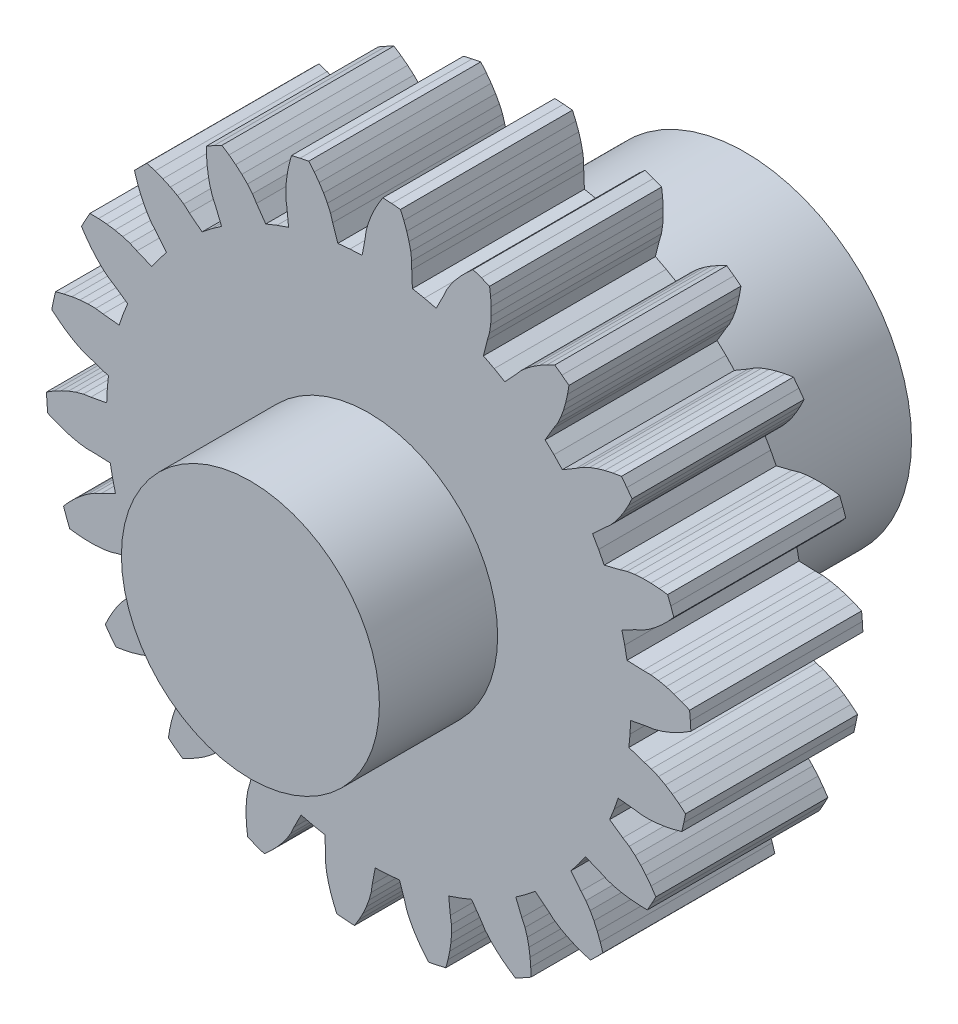
SolidWorks part; units mm, degrees
ref_plane "Front Plane" through (0, 0, 0) normal (0, 0, 1) x (1, 0, 0)
ref_plane "Top Plane" through (0, 0, 0) normal (0, 1, 0) x (1, 0, 0)
ref_plane "Right Plane" through (0, 0, 0) normal (1, 0, 0) x (0, 0, -1)
sketch "Sketch1" plane through (0, 0, 0) normal (0, 0, 1) x (1, 0, 0)
  line L0 (24.3674, -0.607) -> (25.8394, -0.3335)
  line L1 (25.8394, -0.3335) -> (26.5336, -0.2338)
  line L2 (26.5336, -0.2338) -> (27.2277, -0.0399)
  line L3 (27.2277, -0.0399) -> (27.9199, 0.2199)
  line L4 (27.9199, 0.2199) -> (28.6088, 0.536)
  line L5 (28.6088, 0.536) -> (29.293, 0.9035)
  line L6 (29.293, 0.9035) -> (29.971, 1.319)
  line L7 (29.971, 1.319) -> (29.9236, 2.1402)
  line L8 (29.9236, 2.1402) -> (29.8536, 2.9597)
  line L9 (29.8536, 2.9597) -> (29.1234, 3.2745)
  line L10 (29.1234, 3.2745) -> (28.3939, 3.5409)
  line L11 (28.3939, 3.5409) -> (27.667, 3.7558)
  line L12 (27.667, 3.7558) -> (26.9449, 3.9144)
  line L13 (26.9449, 3.9144) -> (26.2302, 4.0076)
  line L14 (26.2302, 4.0076) -> (25.5289, 4.0074)
  line L15 (25.5289, 4.0074) -> (24.033, 4.0687)
  line L16 (24.033, 4.0687) -> (23.818, 5.1813)
  line L17 (23.818, 5.1813) -> (23.5514, 6.2827)
  line L18 (23.5514, 6.2827) -> (24.8867, 6.9598)
  line L19 (24.8867, 6.9598) -> (25.5247, 7.251)
  line L20 (25.5247, 7.251) -> (26.136, 7.6327)
  line L21 (26.136, 7.6327) -> (26.727, 8.0769)
  line L22 (26.727, 8.0769) -> (27.299, 8.5743)
  line L23 (27.299, 8.5743) -> (27.8519, 9.1197)
  line L24 (27.8519, 9.1197) -> (28.3853, 9.7094)
  line L25 (28.3853, 9.7094) -> (28.1085, 10.4839)
  line L26 (28.1085, 10.4839) -> (27.8105, 11.2506)
  line L27 (27.8105, 11.2506) -> (27.0212, 11.3469)
  line L28 (27.0212, 11.3469) -> (26.2462, 11.397)
  line L29 (26.2462, 11.397) -> (25.4882, 11.3984)
  line L30 (25.4882, 11.3984) -> (24.7506, 11.347)
  line L31 (24.7506, 11.347) -> (24.0387, 11.2352)
  line L32 (24.0387, 11.2352) -> (23.3658, 11.0374)
  line L33 (23.3658, 11.0374) -> (21.9133, 10.6747)
  line L34 (21.9133, 10.6747) -> (21.3934, 11.6817)
  line L35 (21.3934, 11.6817) -> (20.8274, 12.6634)
  line L36 (20.8274, 12.6634) -> (21.9178, 13.6893)
  line L37 (21.9178, 13.6893) -> (22.4479, 14.1484)
  line L38 (22.4479, 14.1484) -> (22.9269, 14.6868)
  line L39 (22.9269, 14.6868) -> (23.3689, 15.2796)
  line L40 (23.3689, 15.2796) -> (23.7775, 15.918)
  line L41 (23.7775, 15.918) -> (24.1544, 16.597)
  line L42 (24.1544, 16.597) -> (24.5001, 17.3132)
  line L43 (24.5001, 17.3132) -> (24.0162, 17.9783)
  line L44 (24.0162, 17.9783) -> (23.5144, 18.63)
  line L45 (23.5144, 18.63) -> (22.7298, 18.5)
  line L46 (22.7298, 18.5) -> (21.9721, 18.3297)
  line L47 (21.9721, 18.3297) -> (21.2444, 18.1175)
  line L48 (21.2444, 18.1175) -> (20.5512, 17.8605)
  line L49 (20.5512, 17.8605) -> (19.8996, 17.5525)
  line L50 (19.8996, 17.5525) -> (19.3097, 17.1732)
  line L51 (19.3097, 17.1732) -> (18.0182, 16.416)
  line L52 (18.0182, 16.416) -> (17.2357, 17.2357)
  line L53 (17.2357, 17.2357) -> (16.416, 18.0182)
  line L54 (16.416, 18.0182) -> (17.1732, 19.3097)
  line L55 (17.1732, 19.3097) -> (17.5525, 19.8996)
  line L56 (17.5525, 19.8996) -> (17.8605, 20.5512)
  line L57 (17.8605, 20.5512) -> (18.1175, 21.2444)
  line L58 (18.1175, 21.2444) -> (18.3297, 21.9721)
  line L59 (18.3297, 21.9721) -> (18.5, 22.7298)
  line L60 (18.5, 22.7298) -> (18.63, 23.5144)
  line L61 (18.63, 23.5144) -> (17.9783, 24.0162)
  line L62 (17.9783, 24.0162) -> (17.3132, 24.5001)
  line L63 (17.3132, 24.5001) -> (16.597, 24.1544)
  line L64 (16.597, 24.1544) -> (15.918, 23.7775)
  line L65 (15.918, 23.7775) -> (15.2796, 23.3689)
  line L66 (15.2796, 23.3689) -> (14.6868, 22.9269)
  line L67 (14.6868, 22.9269) -> (14.1484, 22.4479)
  line L68 (14.1484, 22.4479) -> (13.6893, 21.9178)
  line L69 (13.6893, 21.9178) -> (12.6634, 20.8274)
  line L70 (12.6634, 20.8274) -> (11.6817, 21.3934)
  line L71 (11.6817, 21.3934) -> (10.6747, 21.9133)
  line L72 (10.6747, 21.9133) -> (11.0374, 23.3658)
  line L73 (11.0374, 23.3658) -> (11.2352, 24.0387)
  line L74 (11.2352, 24.0387) -> (11.347, 24.7506)
  line L75 (11.347, 24.7506) -> (11.3984, 25.4882)
  line L76 (11.3984, 25.4882) -> (11.397, 26.2462)
  line L77 (11.397, 26.2462) -> (11.3469, 27.0212)
  line L78 (11.3469, 27.0212) -> (11.2506, 27.8105)
  line L79 (11.2506, 27.8105) -> (10.4839, 28.1085)
  line L80 (10.4839, 28.1085) -> (9.7094, 28.3853)
  line L81 (9.7094, 28.3853) -> (9.1197, 27.8519)
  line L82 (9.1197, 27.8519) -> (8.5743, 27.299)
  line L83 (8.5743, 27.299) -> (8.0769, 26.727)
  line L84 (8.0769, 26.727) -> (7.6327, 26.136)
  line L85 (7.6327, 26.136) -> (7.251, 25.5247)
  line L86 (7.251, 25.5247) -> (6.9598, 24.8867)
  line L87 (6.9598, 24.8867) -> (6.2827, 23.5514)
  line L88 (6.2827, 23.5514) -> (5.1813, 23.818)
  line L89 (5.1813, 23.818) -> (4.0687, 24.033)
  line L90 (4.0687, 24.033) -> (4.0074, 25.5289)
  line L91 (4.0074, 25.5289) -> (4.0076, 26.2302)
  line L92 (4.0076, 26.2302) -> (3.9144, 26.9449)
  line L93 (3.9144, 26.9449) -> (3.7558, 27.667)
  line L94 (3.7558, 27.667) -> (3.5409, 28.3939)
  line L95 (3.5409, 28.3939) -> (3.2745, 29.1234)
  line L96 (3.2745, 29.1234) -> (2.9597, 29.8536)
  line L97 (2.9597, 29.8536) -> (2.1402, 29.9236)
  line L98 (2.1402, 29.9236) -> (1.319, 29.971)
  line L99 (1.319, 29.971) -> (0.9035, 29.293)
  line L100 (0.9035, 29.293) -> (0.536, 28.6088)
  line L101 (0.536, 28.6088) -> (0.2199, 27.9199)
  line L102 (0.2199, 27.9199) -> (-0.0399, 27.2277)
  line L103 (-0.0399, 27.2277) -> (-0.2338, 26.5336)
  line L104 (-0.2338, 26.5336) -> (-0.3335, 25.8394)
  line L105 (-0.3335, 25.8394) -> (-0.607, 24.3674)
  line L106 (-0.607, 24.3674) -> (-1.7389, 24.3129)
  line L107 (-1.7389, 24.3129) -> (-2.867, 24.2058)
  line L108 (-2.867, 24.2058) -> (-3.3473, 25.6238)
  line L109 (-3.3473, 25.6238) -> (-3.5447, 26.2968)
  line L110 (-3.5447, 26.2968) -> (-3.8354, 26.9562)
  line L111 (-3.8354, 26.9562) -> (-4.191, 27.6044)
  line L112 (-4.191, 27.6044) -> (-4.602, 28.2413)
  line L113 (-4.602, 28.2413) -> (-5.0631, 28.8663)
  line L114 (-5.0631, 28.8663) -> (-5.5709, 29.4782)
  line L115 (-5.5709, 29.4782) -> (-6.377, 29.3144)
  line L116 (-6.377, 29.3144) -> (-7.1782, 29.1286)
  line L117 (-7.1782, 29.1286) -> (-7.3859, 28.361)
  line L118 (-7.3859, 28.361) -> (-7.5457, 27.601)
  line L119 (-7.5457, 27.601) -> (-7.655, 26.8509)
  line L120 (-7.655, 26.8509) -> (-7.7092, 26.1135)
  line L121 (-7.7092, 26.1135) -> (-7.6997, 25.3929)
  line L122 (-7.6997, 25.3929) -> (-7.5998, 24.6988)
  line L123 (-7.5998, 24.6988) -> (-7.4475, 23.2094)
  line L124 (-7.4475, 23.2094) -> (-8.5182, 22.8381)
  line L125 (-8.5182, 22.8381) -> (-9.5705, 22.4176)
  line L126 (-9.5705, 22.4176) -> (-10.4307, 23.6429)
  line L127 (-10.4307, 23.6429) -> (-10.8098, 24.2329)
  line L128 (-10.8098, 24.2329) -> (-11.2745, 24.7837)
  line L129 (-11.2745, 24.7837) -> (-11.7983, 25.3055)
  line L130 (-11.7983, 25.3055) -> (-12.3721, 25.8008)
  line L131 (-12.3721, 25.8008) -> (-12.9906, 26.2705)
  line L132 (-12.9906, 26.2705) -> (-13.6502, 26.7146)
  line L133 (-13.6502, 26.7146) -> (-14.3775, 26.3304)
  line L134 (-14.3775, 26.3304) -> (-15.0939, 25.9263)
  line L135 (-15.0939, 25.9263) -> (-15.0769, 25.1313)
  line L136 (-15.0769, 25.1313) -> (-15.0162, 24.3571)
  line L137 (-15.0162, 24.3571) -> (-14.9097, 23.6066)
  line L138 (-14.9097, 23.6066) -> (-14.7539, 22.8838)
  line L139 (-14.7539, 22.8838) -> (-14.5419, 22.1951)
  line L140 (-14.5419, 22.1951) -> (-14.2504, 21.5572)
  line L141 (-14.2504, 21.5572) -> (-13.6847, 20.171)
  line L142 (-13.6847, 20.171) -> (-14.6074, 19.5132)
  line L143 (-14.6074, 19.5132) -> (-15.4986, 18.8132)
  line L144 (-15.4986, 18.8132) -> (-16.6692, 19.7465)
  line L145 (-16.6692, 19.7465) -> (-17.1991, 20.2059)
  line L146 (-17.1991, 20.2059) -> (-17.8002, 20.6034)
  line L147 (-17.8002, 20.6034) -> (-18.4498, 20.9565)
  line L148 (-18.4498, 20.9565) -> (-19.1399, 21.2701)
  line L149 (-19.1399, 21.2701) -> (-19.8656, 21.5465)
  line L150 (-19.8656, 21.5465) -> (-20.6237, 21.7868)
  line L151 (-20.6237, 21.7868) -> (-21.2132, 21.2132)
  line L152 (-21.2132, 21.2132) -> (-21.7868, 20.6237)
  line L153 (-21.7868, 20.6237) -> (-21.5465, 19.8656)
  line L154 (-21.5465, 19.8656) -> (-21.2701, 19.1399)
  line L155 (-21.2701, 19.1399) -> (-20.9565, 18.4498)
  line L156 (-20.9565, 18.4498) -> (-20.6034, 17.8002)
  line L157 (-20.6034, 17.8002) -> (-20.2059, 17.1991)
  line L158 (-20.2059, 17.1991) -> (-19.7465, 16.6692)
  line L159 (-19.7465, 16.6692) -> (-18.8132, 15.4986)
  line L160 (-18.8132, 15.4986) -> (-19.5132, 14.6074)
  line L161 (-19.5132, 14.6074) -> (-20.171, 13.6847)
  line L162 (-20.171, 13.6847) -> (-21.5572, 14.2504)
  line L163 (-21.5572, 14.2504) -> (-22.1951, 14.5419)
  line L164 (-22.1951, 14.5419) -> (-22.8838, 14.7539)
  line L165 (-22.8838, 14.7539) -> (-23.6066, 14.9097)
  line L166 (-23.6066, 14.9097) -> (-24.3571, 15.0162)
  line L167 (-24.3571, 15.0162) -> (-25.1313, 15.0769)
  line L168 (-25.1313, 15.0769) -> (-25.9263, 15.0939)
  line L169 (-25.9263, 15.0939) -> (-26.3304, 14.3775)
  line L170 (-26.3304, 14.3775) -> (-26.7146, 13.6502)
  line L171 (-26.7146, 13.6502) -> (-26.2705, 12.9906)
  line L172 (-26.2705, 12.9906) -> (-25.8008, 12.3721)
  line L173 (-25.8008, 12.3721) -> (-25.3055, 11.7983)
  line L174 (-25.3055, 11.7983) -> (-24.7837, 11.2745)
  line L175 (-24.7837, 11.2745) -> (-24.2329, 10.8098)
  line L176 (-24.2329, 10.8098) -> (-23.6429, 10.4307)
  line L177 (-23.6429, 10.4307) -> (-22.4176, 9.5705)
  line L178 (-22.4176, 9.5705) -> (-22.8381, 8.5182)
  line L179 (-22.8381, 8.5182) -> (-23.2094, 7.4475)
  line L180 (-23.2094, 7.4475) -> (-24.6988, 7.5998)
  line L181 (-24.6988, 7.5998) -> (-25.3929, 7.6997)
  line L182 (-25.3929, 7.6997) -> (-26.1135, 7.7092)
  line L183 (-26.1135, 7.7092) -> (-26.8509, 7.655)
  line L184 (-26.8509, 7.655) -> (-27.601, 7.5457)
  line L185 (-27.601, 7.5457) -> (-28.361, 7.3859)
  line L186 (-28.361, 7.3859) -> (-29.1286, 7.1782)
  line L187 (-29.1286, 7.1782) -> (-29.3144, 6.377)
  line L188 (-29.3144, 6.377) -> (-29.4782, 5.5709)
  line L189 (-29.4782, 5.5709) -> (-28.8663, 5.0631)
  line L190 (-28.8663, 5.0631) -> (-28.2413, 4.602)
  line L191 (-28.2413, 4.602) -> (-27.6044, 4.191)
  line L192 (-27.6044, 4.191) -> (-26.9562, 3.8354)
  line L193 (-26.9562, 3.8354) -> (-26.2968, 3.5447)
  line L194 (-26.2968, 3.5447) -> (-25.6238, 3.3473)
  line L195 (-25.6238, 3.3473) -> (-24.2058, 2.867)
  line L196 (-24.2058, 2.867) -> (-24.3129, 1.7389)
  line L197 (-24.3129, 1.7389) -> (-24.3674, 0.607)
  line L198 (-24.3674, 0.607) -> (-25.8394, 0.3335)
  line L199 (-25.8394, 0.3335) -> (-26.5336, 0.2338)
  line L200 (-26.5336, 0.2338) -> (-27.2277, 0.0399)
  line L201 (-27.2277, 0.0399) -> (-27.9199, -0.2199)
  line L202 (-27.9199, -0.2199) -> (-28.6088, -0.536)
  line L203 (-28.6088, -0.536) -> (-29.293, -0.9035)
  line L204 (-29.293, -0.9035) -> (-29.971, -1.319)
  line L205 (-29.971, -1.319) -> (-29.9236, -2.1402)
  line L206 (-29.9236, -2.1402) -> (-29.8536, -2.9597)
  line L207 (-29.8536, -2.9597) -> (-29.1234, -3.2745)
  line L208 (-29.1234, -3.2745) -> (-28.3939, -3.5409)
  line L209 (-28.3939, -3.5409) -> (-27.667, -3.7558)
  line L210 (-27.667, -3.7558) -> (-26.9449, -3.9144)
  line L211 (-26.9449, -3.9144) -> (-26.2302, -4.0076)
  line L212 (-26.2302, -4.0076) -> (-25.5289, -4.0074)
  line L213 (-25.5289, -4.0074) -> (-24.033, -4.0687)
  line L214 (-24.033, -4.0687) -> (-23.818, -5.1813)
  line L215 (-23.818, -5.1813) -> (-23.5514, -6.2827)
  line L216 (-23.5514, -6.2827) -> (-24.8867, -6.9598)
  line L217 (-24.8867, -6.9598) -> (-25.5247, -7.251)
  line L218 (-25.5247, -7.251) -> (-26.136, -7.6327)
  line L219 (-26.136, -7.6327) -> (-26.727, -8.0769)
  line L220 (-26.727, -8.0769) -> (-27.299, -8.5743)
  line L221 (-27.299, -8.5743) -> (-27.8519, -9.1197)
  line L222 (-27.8519, -9.1197) -> (-28.3853, -9.7094)
  line L223 (-28.3853, -9.7094) -> (-28.1085, -10.4839)
  line L224 (-28.1085, -10.4839) -> (-27.8105, -11.2506)
  line L225 (-27.8105, -11.2506) -> (-27.0212, -11.3469)
  line L226 (-27.0212, -11.3469) -> (-26.2462, -11.397)
  line L227 (-26.2462, -11.397) -> (-25.4882, -11.3984)
  line L228 (-25.4882, -11.3984) -> (-24.7506, -11.347)
  line L229 (-24.7506, -11.347) -> (-24.0387, -11.2352)
  line L230 (-24.0387, -11.2352) -> (-23.3658, -11.0374)
  line L231 (-23.3658, -11.0374) -> (-21.9133, -10.6747)
  line L232 (-21.9133, -10.6747) -> (-21.3934, -11.6817)
  line L233 (-21.3934, -11.6817) -> (-20.8274, -12.6634)
  line L234 (-20.8274, -12.6634) -> (-21.9178, -13.6893)
  line L235 (-21.9178, -13.6893) -> (-22.4479, -14.1484)
  line L236 (-22.4479, -14.1484) -> (-22.9269, -14.6868)
  line L237 (-22.9269, -14.6868) -> (-23.3689, -15.2796)
  line L238 (-23.3689, -15.2796) -> (-23.7775, -15.918)
  line L239 (-23.7775, -15.918) -> (-24.1544, -16.597)
  line L240 (-24.1544, -16.597) -> (-24.5001, -17.3132)
  line L241 (-24.5001, -17.3132) -> (-24.0162, -17.9783)
  line L242 (-24.0162, -17.9783) -> (-23.5144, -18.63)
  line L243 (-23.5144, -18.63) -> (-22.7298, -18.5)
  line L244 (-22.7298, -18.5) -> (-21.9721, -18.3297)
  line L245 (-21.9721, -18.3297) -> (-21.2444, -18.1175)
  line L246 (-21.2444, -18.1175) -> (-20.5512, -17.8605)
  line L247 (-20.5512, -17.8605) -> (-19.8996, -17.5525)
  line L248 (-19.8996, -17.5525) -> (-19.3097, -17.1732)
  line L249 (-19.3097, -17.1732) -> (-18.0182, -16.416)
  line L250 (-18.0182, -16.416) -> (-17.2357, -17.2357)
  line L251 (-17.2357, -17.2357) -> (-16.416, -18.0182)
  line L252 (-16.416, -18.0182) -> (-17.1732, -19.3097)
  line L253 (-17.1732, -19.3097) -> (-17.5525, -19.8996)
  line L254 (-17.5525, -19.8996) -> (-17.8605, -20.5512)
  line L255 (-17.8605, -20.5512) -> (-18.1175, -21.2444)
  line L256 (-18.1175, -21.2444) -> (-18.3297, -21.9721)
  line L257 (-18.3297, -21.9721) -> (-18.5, -22.7298)
  line L258 (-18.5, -22.7298) -> (-18.63, -23.5144)
  line L259 (-18.63, -23.5144) -> (-17.9783, -24.0162)
  line L260 (-17.9783, -24.0162) -> (-17.3132, -24.5001)
  line L261 (-17.3132, -24.5001) -> (-16.597, -24.1544)
  line L262 (-16.597, -24.1544) -> (-15.918, -23.7775)
  line L263 (-15.918, -23.7775) -> (-15.2796, -23.3689)
  line L264 (-15.2796, -23.3689) -> (-14.6868, -22.9269)
  line L265 (-14.6868, -22.9269) -> (-14.1484, -22.4479)
  line L266 (-14.1484, -22.4479) -> (-13.6893, -21.9178)
  line L267 (-13.6893, -21.9178) -> (-12.6634, -20.8274)
  line L268 (-12.6634, -20.8274) -> (-11.6817, -21.3934)
  line L269 (-11.6817, -21.3934) -> (-10.6747, -21.9133)
  line L270 (-10.6747, -21.9133) -> (-11.0374, -23.3658)
  line L271 (-11.0374, -23.3658) -> (-11.2352, -24.0387)
  line L272 (-11.2352, -24.0387) -> (-11.347, -24.7506)
  line L273 (-11.347, -24.7506) -> (-11.3984, -25.4882)
  line L274 (-11.3984, -25.4882) -> (-11.397, -26.2462)
  line L275 (-11.397, -26.2462) -> (-11.3469, -27.0212)
  line L276 (-11.3469, -27.0212) -> (-11.2506, -27.8105)
  line L277 (-11.2506, -27.8105) -> (-10.4839, -28.1085)
  line L278 (-10.4839, -28.1085) -> (-9.7094, -28.3853)
  line L279 (-9.7094, -28.3853) -> (-9.1197, -27.8519)
  line L280 (-9.1197, -27.8519) -> (-8.5743, -27.299)
  line L281 (-8.5743, -27.299) -> (-8.0769, -26.727)
  line L282 (-8.0769, -26.727) -> (-7.6327, -26.136)
  line L283 (-7.6327, -26.136) -> (-7.251, -25.5247)
  line L284 (-7.251, -25.5247) -> (-6.9598, -24.8867)
  line L285 (-6.9598, -24.8867) -> (-6.2827, -23.5514)
  line L286 (-6.2827, -23.5514) -> (-5.1813, -23.818)
  line L287 (-5.1813, -23.818) -> (-4.0687, -24.033)
  line L288 (-4.0687, -24.033) -> (-4.0074, -25.5289)
  line L289 (-4.0074, -25.5289) -> (-4.0076, -26.2302)
  line L290 (-4.0076, -26.2302) -> (-3.9144, -26.9449)
  line L291 (-3.9144, -26.9449) -> (-3.7558, -27.667)
  line L292 (-3.7558, -27.667) -> (-3.5409, -28.3939)
  line L293 (-3.5409, -28.3939) -> (-3.2745, -29.1234)
  line L294 (-3.2745, -29.1234) -> (-2.9597, -29.8536)
  line L295 (-2.9597, -29.8536) -> (-2.1402, -29.9236)
  line L296 (-2.1402, -29.9236) -> (-1.319, -29.971)
  line L297 (-1.319, -29.971) -> (-0.9035, -29.293)
  line L298 (-0.9035, -29.293) -> (-0.536, -28.6088)
  line L299 (-0.536, -28.6088) -> (-0.2199, -27.9199)
  line L300 (-0.2199, -27.9199) -> (0.0399, -27.2277)
  line L301 (0.0399, -27.2277) -> (0.2338, -26.5336)
  line L302 (0.2338, -26.5336) -> (0.3335, -25.8394)
  line L303 (0.3335, -25.8394) -> (0.607, -24.3674)
  line L304 (0.607, -24.3674) -> (1.7389, -24.3129)
  line L305 (1.7389, -24.3129) -> (2.867, -24.2058)
  line L306 (2.867, -24.2058) -> (3.3473, -25.6238)
  line L307 (3.3473, -25.6238) -> (3.5447, -26.2968)
  line L308 (3.5447, -26.2968) -> (3.8354, -26.9562)
  line L309 (3.8354, -26.9562) -> (4.191, -27.6044)
  line L310 (4.191, -27.6044) -> (4.602, -28.2413)
  line L311 (4.602, -28.2413) -> (5.0631, -28.8663)
  line L312 (5.0631, -28.8663) -> (5.5709, -29.4782)
  line L313 (5.5709, -29.4782) -> (6.377, -29.3144)
  line L314 (6.377, -29.3144) -> (7.1782, -29.1286)
  line L315 (7.1782, -29.1286) -> (7.3859, -28.361)
  line L316 (7.3859, -28.361) -> (7.5457, -27.601)
  line L317 (7.5457, -27.601) -> (7.655, -26.8509)
  line L318 (7.655, -26.8509) -> (7.7092, -26.1135)
  line L319 (7.7092, -26.1135) -> (7.6997, -25.3929)
  line L320 (7.6997, -25.3929) -> (7.5998, -24.6988)
  line L321 (7.5998, -24.6988) -> (7.4475, -23.2094)
  line L322 (7.4475, -23.2094) -> (8.5182, -22.8381)
  line L323 (8.5182, -22.8381) -> (9.5705, -22.4176)
  line L324 (9.5705, -22.4176) -> (10.4307, -23.6429)
  line L325 (10.4307, -23.6429) -> (10.8098, -24.2329)
  line L326 (10.8098, -24.2329) -> (11.2745, -24.7837)
  line L327 (11.2745, -24.7837) -> (11.7983, -25.3055)
  line L328 (11.7983, -25.3055) -> (12.3721, -25.8008)
  line L329 (12.3721, -25.8008) -> (12.9906, -26.2705)
  line L330 (12.9906, -26.2705) -> (13.6502, -26.7146)
  line L331 (13.6502, -26.7146) -> (14.3775, -26.3304)
  line L332 (14.3775, -26.3304) -> (15.0939, -25.9263)
  line L333 (15.0939, -25.9263) -> (15.0769, -25.1313)
  line L334 (15.0769, -25.1313) -> (15.0162, -24.3571)
  line L335 (15.0162, -24.3571) -> (14.9097, -23.6066)
  line L336 (14.9097, -23.6066) -> (14.7539, -22.8838)
  line L337 (14.7539, -22.8838) -> (14.5419, -22.1951)
  line L338 (14.5419, -22.1951) -> (14.2504, -21.5572)
  line L339 (14.2504, -21.5572) -> (13.6847, -20.171)
  line L340 (13.6847, -20.171) -> (14.6074, -19.5132)
  line L341 (14.6074, -19.5132) -> (15.4986, -18.8132)
  line L342 (15.4986, -18.8132) -> (16.6692, -19.7465)
  line L343 (16.6692, -19.7465) -> (17.1991, -20.2059)
  line L344 (17.1991, -20.2059) -> (17.8002, -20.6034)
  line L345 (17.8002, -20.6034) -> (18.4498, -20.9565)
  line L346 (18.4498, -20.9565) -> (19.1399, -21.2701)
  line L347 (19.1399, -21.2701) -> (19.8656, -21.5465)
  line L348 (19.8656, -21.5465) -> (20.6237, -21.7868)
  line L349 (20.6237, -21.7868) -> (21.2132, -21.2132)
  line L350 (21.2132, -21.2132) -> (21.7868, -20.6237)
  line L351 (21.7868, -20.6237) -> (21.5465, -19.8656)
  line L352 (21.5465, -19.8656) -> (21.2701, -19.1399)
  line L353 (21.2701, -19.1399) -> (20.9565, -18.4498)
  line L354 (20.9565, -18.4498) -> (20.6034, -17.8002)
  line L355 (20.6034, -17.8002) -> (20.2059, -17.1991)
  line L356 (20.2059, -17.1991) -> (19.7465, -16.6692)
  line L357 (19.7465, -16.6692) -> (18.8132, -15.4986)
  line L358 (18.8132, -15.4986) -> (19.5132, -14.6074)
  line L359 (19.5132, -14.6074) -> (20.171, -13.6847)
  line L360 (20.171, -13.6847) -> (21.5572, -14.2504)
  line L361 (21.5572, -14.2504) -> (22.1951, -14.5419)
  line L362 (22.1951, -14.5419) -> (22.8838, -14.7539)
  line L363 (22.8838, -14.7539) -> (23.6066, -14.9097)
  line L364 (23.6066, -14.9097) -> (24.3571, -15.0162)
  line L365 (24.3571, -15.0162) -> (25.1313, -15.0769)
  line L366 (25.1313, -15.0769) -> (25.9263, -15.0939)
  line L367 (25.9263, -15.0939) -> (26.3304, -14.3775)
  line L368 (26.3304, -14.3775) -> (26.7146, -13.6502)
  line L369 (26.7146, -13.6502) -> (26.2705, -12.9906)
  line L370 (26.2705, -12.9906) -> (25.8008, -12.3721)
  line L371 (25.8008, -12.3721) -> (25.3055, -11.7983)
  line L372 (25.3055, -11.7983) -> (24.7837, -11.2745)
  line L373 (24.7837, -11.2745) -> (24.2329, -10.8098)
  line L374 (24.2329, -10.8098) -> (23.6429, -10.4307)
  line L375 (23.6429, -10.4307) -> (22.4176, -9.5705)
  line L376 (22.4176, -9.5705) -> (22.8381, -8.5182)
  line L377 (22.8381, -8.5182) -> (23.2094, -7.4475)
  line L378 (23.2094, -7.4475) -> (24.6988, -7.5998)
  line L379 (24.6988, -7.5998) -> (25.3929, -7.6997)
  line L380 (25.3929, -7.6997) -> (26.1135, -7.7092)
  line L381 (26.1135, -7.7092) -> (26.8509, -7.655)
  line L382 (26.8509, -7.655) -> (27.601, -7.5457)
  line L383 (27.601, -7.5457) -> (28.361, -7.3859)
  line L384 (28.361, -7.3859) -> (29.1286, -7.1782)
  line L385 (29.1286, -7.1782) -> (29.3144, -6.377)
  line L386 (29.3144, -6.377) -> (29.4782, -5.5709)
  line L387 (29.4782, -5.5709) -> (28.8663, -5.0631)
  line L388 (28.8663, -5.0631) -> (28.2413, -4.602)
  line L389 (28.2413, -4.602) -> (27.6044, -4.191)
  line L390 (27.6044, -4.191) -> (26.9562, -3.8354)
  line L391 (26.9562, -3.8354) -> (26.2968, -3.5447)
  line L392 (26.2968, -3.5447) -> (25.6238, -3.3473)
  line L393 (25.6238, -3.3473) -> (24.2058, -2.867)
  line L394 (24.2058, -2.867) -> (24.3129, -1.7389)
  line L395 (24.3129, -1.7389) -> (24.3674, -0.607)
extrude "22 tooth module 2.5 reference involute" add sketch "Sketch1" along normal blind 16 from offset 42
sketch "Sketch2" plane through (0, 0, 0) normal (0, 0, 1) x (1, 0, 0)
  circle A0 centre (0, 0) radius 12
extrude "Upper bearing journal" add sketch "Sketch2" along normal blind 11 from offset 58
sketch "Sketch3" plane through (0, 0, 0) normal (0, 0, 1) x (1, 0, 0)
  circle A0 centre (0, 0) radius 15.5
extrude "Lower bearing journal" add sketch "Sketch3" against normal blind 19 from offset 42
sketch "Sketch4" plane through (0, 0, 0) normal (0, 0, 1) x (1, 0, 0)
  line L0 (1.02, 12.5565) -> (-1.02, 12.5565)
  line L1 (-1.02, 12.5565) -> (-12.5565, 1.02)
  line L2 (-12.5565, 1.02) -> (-12.5565, -1.02)
  line L3 (-12.5565, -1.02) -> (-1.02, -12.5565)
  line L4 (-1.02, -12.5565) -> (1.02, -12.5565)
  line L5 (1.02, -12.5565) -> (12.5565, -1.02)
  line L6 (12.5565, -1.02) -> (12.5565, 1.02)
  line L7 (12.5565, 1.02) -> (1.02, 12.5565)
extrude "Drive socket from underside" cut sketch "Sketch4" along normal blind 10 from offset 23
